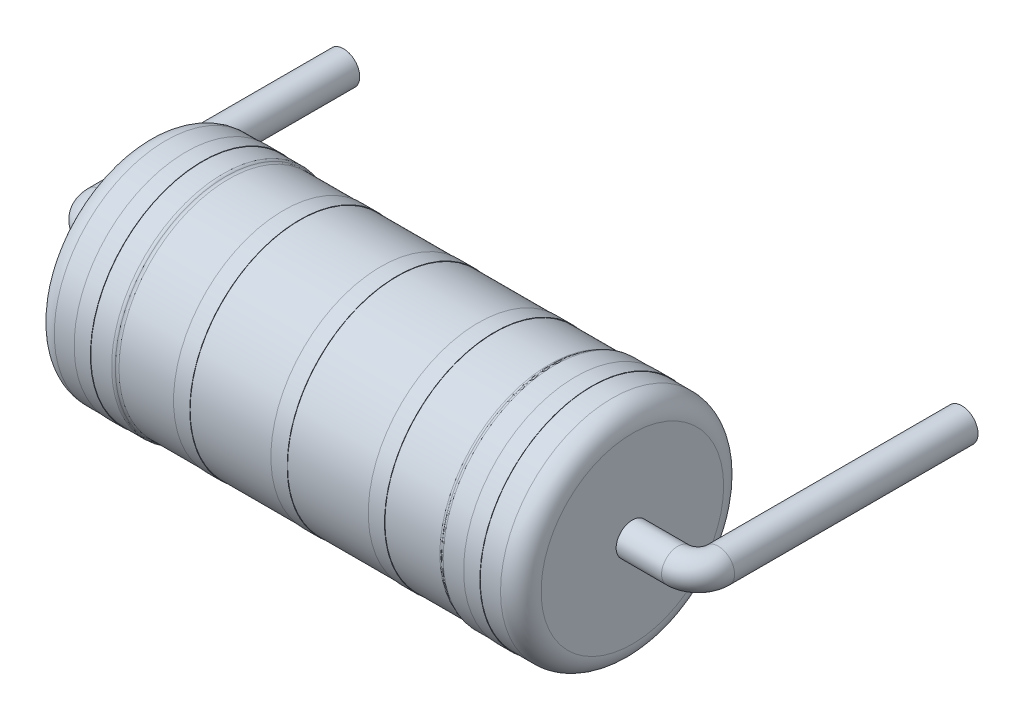
SolidWorks part; units mm, degrees
ref_plane "前视基准面" through (0, 0, 0) normal (0, 0, 1) x (1, 0, 0)
ref_plane "上视基准面" through (0, 0, 0) normal (0, 1, 0) x (1, 0, 0)
ref_plane "右视基准面" through (0, 0, 0) normal (1, 0, 0) x (0, 0, -1)
sketch "草图1" plane through (0, 0, 0) normal (1, 0, 0) x (0, 0, -1)
  line L0 (0, 0) -> (-4.2709, 0) construction
  circle A0 centre (-4.5, 0) radius 2.75
  dimension "D1" = 5.5
  dimension "D2" = 4.5
extrude "拉伸1" add sketch "草图1" along normal mid plane 12
sketch "草图5" plane through (0, 0, 0) normal (1, 0, 0) x (0, 0, -1)
  circle A0 centre (-4.5, 0) radius 2.7
  circle A1 centre (-4.5, 0) radius 2.75 construction
  dimension "D1" = 0.05
extrude "切除-拉伸2" cut sketch "草图5" against normal mid plane 8 flip side to cut
fillet "圆角10" radius 0.1 2 edges at (4, 0, 1.75) (-4, 0, 1.75)
fillet "圆角11" radius 0.1 2 edges at (4, 0, 1.8) (-4, 0, 1.8)
fillet "圆角13" radius 0.5 2 edges at (-6, 0, 1.75) (6, 0, 1.75)
ref_plane "基准面2" through (2.4, 0, 0) normal (1, 0, 0) x (0, 0, -1)
ref_plane "基准面3" through (4.8, 0, 0) normal (1, 0, 0) x (0, 0, -1)
ref_plane "基准面4" through (-2.4, 0, 0) normal (1, 0, 0) x (0, 0, -1)
ref_plane "基准面5" through (-4.8, 0, 0) normal (1, 0, 0) x (0, 0, -1)
sketch "草图6" plane through (4.8, 0, 0) normal (1, 0, 0) x (0, 0, -1)
  circle A0 centre (-4.5, 0) radius 2.76
  circle A2 centre (-4.5, 0) radius 2.75 construction
  dimension "D1" = 0.01
extrude "拉伸2" add sketch "草图6" along normal mid plane 0.4 separate body
sketch "草图7" plane through (-4.8, 0, 0) normal (1, 0, 0) x (0, 0, -1)
  circle A0 centre (-4.5, 0) radius 2.76 construction
  circle A1 centre (-4.5, 0) radius 2.76
extrude "拉伸3" add sketch "草图7" along normal mid plane 0.4 separate body
sketch "草图8" plane through (2.4, 0, 0) normal (1, 0, 0) x (0, 0, -1)
  circle A1 centre (-4.5, 0) radius 2.71
  circle A3 centre (-4.5, 0) radius 2.7 construction
  dimension "D1" = 0.01
extrude "拉伸4" add sketch "草图8" along normal mid plane 0.4 separate body
sketch "草图9" plane through (-2.4, 0, 0) normal (1, 0, 0) x (0, 0, -1)
  circle A0 centre (-4.5, 0) radius 2.71 construction
  circle A1 centre (-4.5, 0) radius 2.71
extrude "拉伸5" add sketch "草图9" along normal mid plane 0.4 separate body
sketch "草图10" plane through (0, 0, 0) normal (1, 0, 0) x (0, 0, -1)
  circle A0 centre (-4.5, 0) radius 2.71 construction
  circle A1 centre (-4.5, 0) radius 2.71
extrude "拉伸6" add sketch "草图10" along normal mid plane 0.4 separate body
sketch "草图12" plane through (0, 0, 0) normal (0, 1, 0) x (1, 0, 0)
  line L0 (-7.12, -4.5) -> (-6, -4.5)
  line L3 (-7.62, -4) -> (-7.62, 2)
  line L5 (-6, -2.25) -> (-6, -6.75) construction
  arc A0 (-7.62, -4) -> (-7.12, -4.5) centre (-7.12, -4) ccw
  dimension "D6" = 0.5
  dimension "D1" = 7.62
  dimension "D5" = 2
sketch "草图13" plane through (-6, 0, 0) normal (1, 0, 0) x (0, 0, -1)
  circle A0 centre (-4.5, 0) radius 0.4
  dimension "D1" = 0.8
sweep "扫描1" add profiles "草图13" path "草图12"
mirror "镜向3" about plane through (0, 0, 0) normal (1, 0, 0) of "扫描1"
